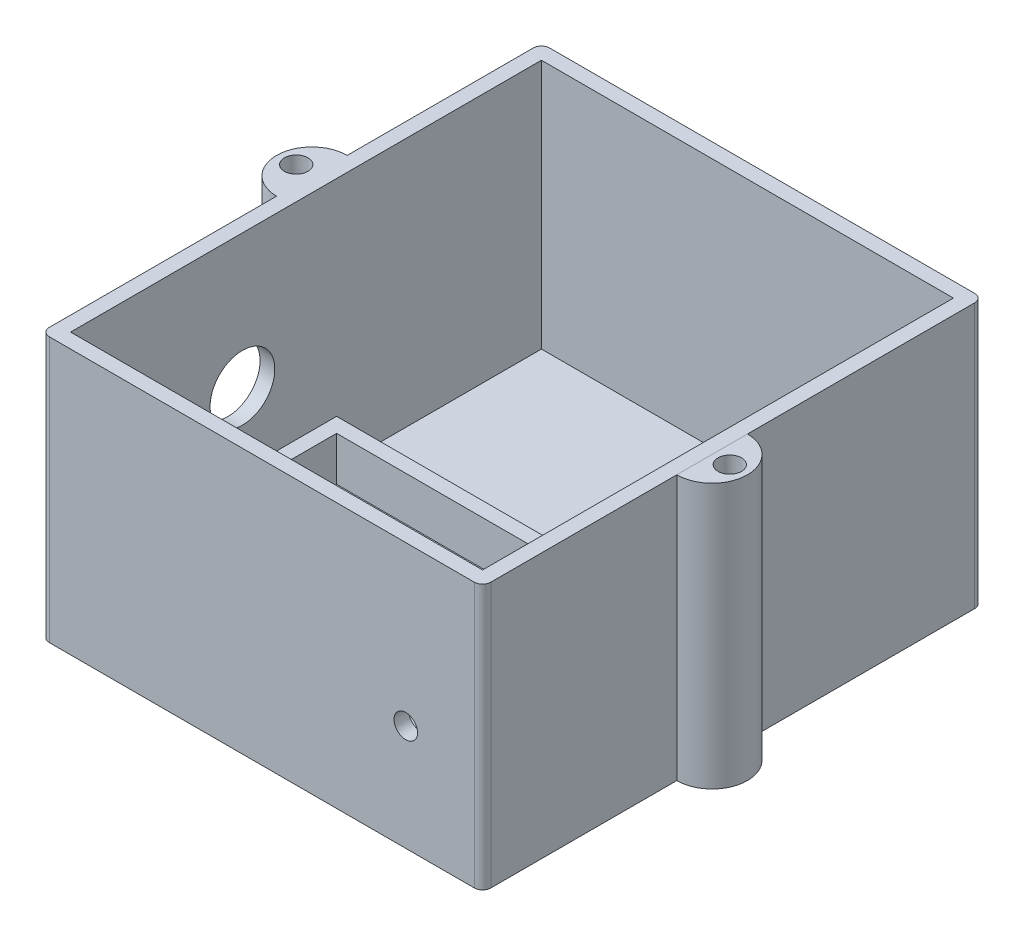
SolidWorks part; units mm, degrees
ref_plane "Front Plane" through (0, 0, 0) normal (0, 0, 1) x (1, 0, 0)
ref_plane "Top Plane" through (0, 0, 0) normal (0, 1, 0) x (1, 0, 0)
ref_plane "Right Plane" through (0, 0, 0) normal (1, 0, 0) x (0, 0, -1)
sketch "Sketch1" plane through (0, 0, 0) normal (0, 1, 0) x (1, 0, 0)
  line L1 (0, 0) -> (-95.25, 0)
  line L2 (0, 0) -> (0, -107.95)
  line L3 (0, -107.95) -> (-95.25, -107.95)
  line L4 (-95.25, 0) -> (-95.25, -107.95)
  line L5 (-3.175, -3.175) -> (-92.075, -3.175)
  line L6 (-3.175, -3.175) -> (-3.175, -104.775)
  line L7 (-3.175, -104.775) -> (-92.075, -104.775)
  line L8 (-92.075, -3.175) -> (-92.075, -104.775)
  dimension "D1" = 107.95
  dimension "D2" = 95.25
  dimension "D3" = 88.9
  dimension "D4" = 101.6
  dimension "D5" = 3.175
  dimension "D6" = 3.175
extrude "Boss-Extrude1" add sketch "Sketch1" along normal blind 3.175 contours L4 L3 L2 L1
extrude "Boss-Extrude2" add sketch "Sketch1<3>" along normal blind 57.15
sketch "Sketch1<3>" plane through (0, 0, 0) normal (0, 1, 0) x (1, 0, 0) same geometry as "Sketch1"
sketch "Sketch3" plane through (0, 0, 107.95) normal (0, 0, 1) x (1, 0, 0)
  line L0 (0, 0) -> (-95.25, 0) construction
  line L1 (0, 57.15) -> (0, 0) construction
  circle A0 centre (-16.5661, 22.86) radius 2.54
  dimension "D1" = 5.08
  dimension "D2" = 22.86
  dimension "D3" = 16.5661
extrude "Cut-Extrude1" cut sketch "Sketch3" against normal blind 12.7
fillet "Fillet1" radius 1.778 4 edges at (-95.25, 28.575, 0) (0, 28.575, 0) (0, 28.575, 107.95) (-95.25, 28.575, 107.95)
sketch "Sketch5" plane through (0, 0, 0) normal (1, 0, 0) x (0, 0, -1)
  line L0 (-106.172, 57.15) -> (-1.778, 57.15) construction
  line L1 (-66.04, 57.15) -> (-58.42, 57.15)
  line L2 (-66.04, 57.15) -> (-66.04, 0)
  line L3 (-66.04, 0) -> (-58.42, 0)
  line L4 (-58.42, 57.15) -> (-58.42, 0)
  line L5 (-1.778, 0) -> (-106.172, 0) construction
  line L7 (0, 57.15) -> (0, 0) construction
  dimension "D1" = 7.62
  dimension "D2" = 58.42
revolve "Revolve1" add sketch "Sketch5" angle 180 about L4 reverse direction yes
sketch "Sketch6" plane through (-95.25, 0, 0) normal (-1, 0, 0) x (0, 0, 1)
  line L0 (1.778, 57.15) -> (106.172, 57.15) construction
  line L1 (49.53, 57.15) -> (57.15, 57.15)
  line L2 (49.53, 57.15) -> (49.53, 0)
  line L3 (49.53, 0) -> (57.15, 0)
  line L4 (57.15, 57.15) -> (57.15, 0)
  line L5 (1.778, 0) -> (106.172, 0) construction
  line L7 (107.95, 57.15) -> (107.95, 0) construction
  dimension "D1" = 7.62
  dimension "D2" = 50.8
revolve "Revolve2" add sketch "Sketch6" angle 180 about L2
sketch "Sketch7" plane through (0, 57.15, 0) normal (0, 1, 0) x (1, 0, 0)
  circle A0 centre (-99.039, -49.1303) radius 2.54
  arc A9 (-95.25, -41.91) -> (-95.25, -57.15) centre (-95.25, -49.53) ccw construction
  dimension "D1" = 5.08
  dimension "D2" = 3.81
  dimension "D3" = 3.789
extrude "Cut-Extrude2" cut sketch "Sketch7" against normal through all
sketch "Sketch9" plane through (0, 57.15, 0) normal (0, 1, 0) x (1, 0, 0)
  line L0 (0, -106.172) -> (0, -1.778) construction
  circle A0 centre (3.81, -58.42) radius 2.54
  arc A1 (0, -66.04) -> (0, -50.8) centre (0, -58.42) ccw construction
  dimension "D1" = 5.08
  dimension "D2" = 3.81
  dimension "D3" = 3.81
extrude "Cut-Extrude3" cut sketch "Sketch9" against normal through all
sketch "Sketch10" plane through (0, 3.175, 0) normal (0, 1, 0) x (1, 0, 0)
  line L0 (-92.075, -104.775) -> (-92.075, -3.175) construction
  line L1 (-92.075, -104.775) -> (-4.191, -104.775)
  line L2 (-92.075, -104.775) -> (-92.075, -47.371)
  line L3 (-92.075, -47.371) -> (-4.191, -47.371)
  line L4 (-4.191, -104.775) -> (-4.191, -47.371)
  line L6 (-88.9, -101.6) -> (-7.366, -101.6)
  line L7 (-88.9, -101.6) -> (-88.9, -50.546)
  line L8 (-88.9, -50.546) -> (-7.366, -50.546)
  line L9 (-7.366, -101.6) -> (-7.366, -50.546)
  dimension "D1" = 3.175
  dimension "D2" = 3.175
  dimension "D3" = 3.175
  dimension "D4" = 3.175
  dimension "D5" = 51.054
  dimension "D6" = 81.534
extrude "Boss-Extrude3" add sketch "Sketch10" along normal blind 9.525
sketch "Sketch11" plane through (0, 3.175, 0) normal (0, 1, 0) x (1, 0, 0)
  line L0 (-73.533, -74.4855) -> (-73.533, -50.546) construction
  line L1 (-22.733, -74.4855) -> (-73.533, -74.4855)
  line L2 (-22.733, -74.4855) -> (-22.733, -77.6605)
  line L3 (-22.733, -77.6605) -> (-73.533, -77.6605)
  line L4 (-73.533, -74.4855) -> (-73.533, -77.6605)
  line L5 (-7.366, -50.546) -> (-88.9, -50.546) construction
  line L6 (-73.533, -77.6605) -> (-73.533, -101.6) construction
  line L7 (-88.9, -101.6) -> (-7.366, -101.6) construction
  line L8 (-73.533, -75.356) -> (-88.9, -75.356) construction
  line L9 (-88.9, -50.546) -> (-88.9, -101.6) construction
  line L10 (-22.733, -75.356) -> (-7.366, -75.356) construction
  line L11 (-7.366, -101.6) -> (-7.366, -50.546) construction
  dimension "D1" = 3.175
  dimension "D2" = 50.8
extrude "Boss-Extrude4" add sketch "Sketch11" along normal blind 7.62
sketch "Sketch12" plane through (-95.25, 0, 0) normal (-1, 0, 0) x (0, 0, 1)
  line L0 (107.95, 57.15) -> (107.95, 0) construction
  line L1 (57.15, 0) -> (106.172, 0) construction
  circle A0 centre (67.691, 28.194) radius 6.985
  dimension "D1" = 13.97
  dimension "D2" = 40.259
  dimension "D3" = 28.194
extrude "Cut-Extrude4" cut sketch "Sketch12" against normal blind 7.62
